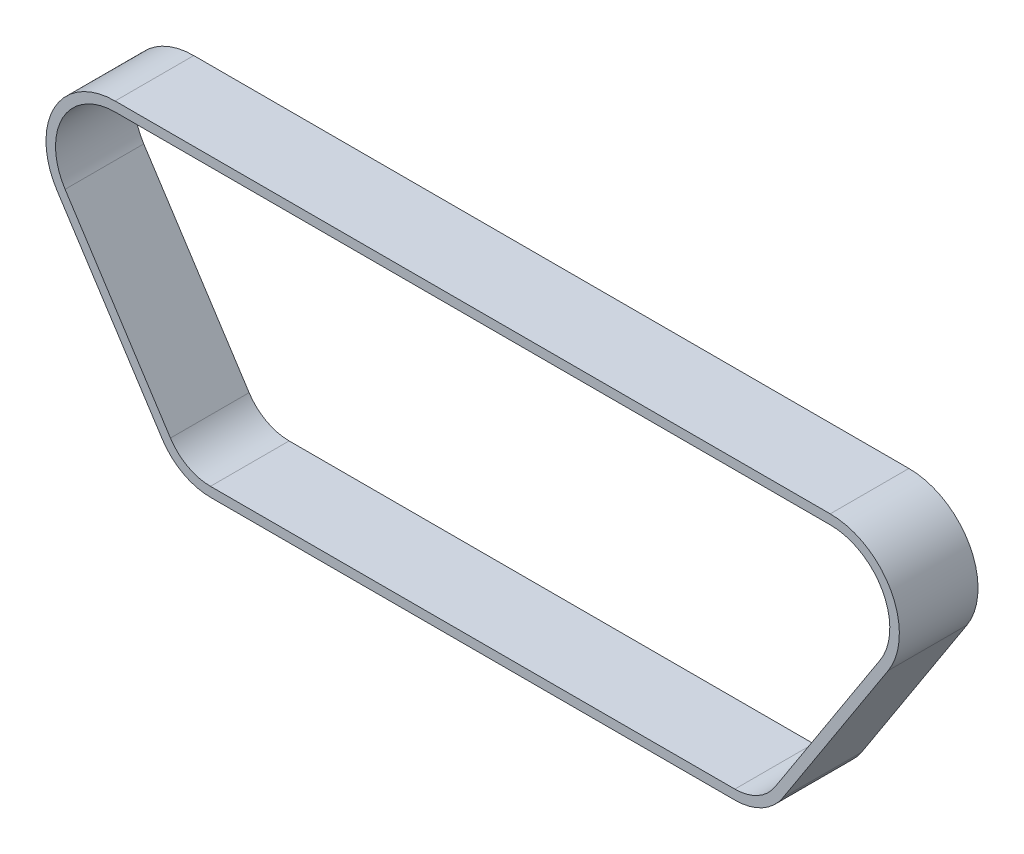
SolidWorks part; units mm, degrees
ref_plane "Front Plane" through (0, 0, 0) normal (0, 0, 1) x (1, 0, 0)
ref_plane "Top Plane" through (0, 0, 0) normal (0, 1, 0) x (1, 0, 0)
ref_plane "Right Plane" through (0, 0, 0) normal (1, 0, 0) x (0, 0, -1)
sketch "Sketch1" plane through (0, 0, 0) normal (0, 0, 1) x (1, 0, 0)
  line L0 (-150, 12.5) -> (0, 12.5)
  line L1 (10.4936, -6.7922) -> (-11.6051, -40.9337)
  line L2 (-160.4936, -6.7922) -> (-138.3949, -40.9337)
  line L3 (-130, -45.5) -> (-20, -45.5)
  line L4 (-130, -47.5) -> (-20, -47.5)
  line L5 (12.1726, -7.8789) -> (-9.9261, -42.0205)
  line L6 (-150, 14.5) -> (0, 14.5)
  line L7 (-162.1726, -7.8789) -> (-140.0739, -42.0205)
  circle A0 centre (-150, 0) radius 12.5 construction
  arc A1 (-150, 12.5) -> (-160.4936, -6.7922) centre (-150, 0) ccw
  circle A2 centre (0, 0) radius 12.5 construction
  arc A3 (10.4936, -6.7922) -> (0, 12.5) centre (0, 0) ccw
  circle A4 centre (-20, -35.5) radius 10 construction
  arc A5 (-20, -45.5) -> (-11.6051, -40.9337) centre (-20, -35.5) ccw
  circle A6 centre (-130, -35.5) radius 10 construction
  arc A7 (-138.3949, -40.9337) -> (-130, -45.5) centre (-130, -35.5) ccw
  arc A8 (-20, -47.5) -> (-9.9261, -42.0205) centre (-20, -35.5) ccw
  arc A9 (12.1726, -7.8789) -> (0, 14.5) centre (0, 0) ccw
  arc A10 (-150, 14.5) -> (-162.1726, -7.8789) centre (-150, 0) ccw
  arc A11 (-140.0739, -42.0205) -> (-130, -47.5) centre (-130, -35.5) ccw
  dimension "D1" = 2
extrude "Boss-Extrude1" add sketch "Sketch1" along normal mid plane 16.5
